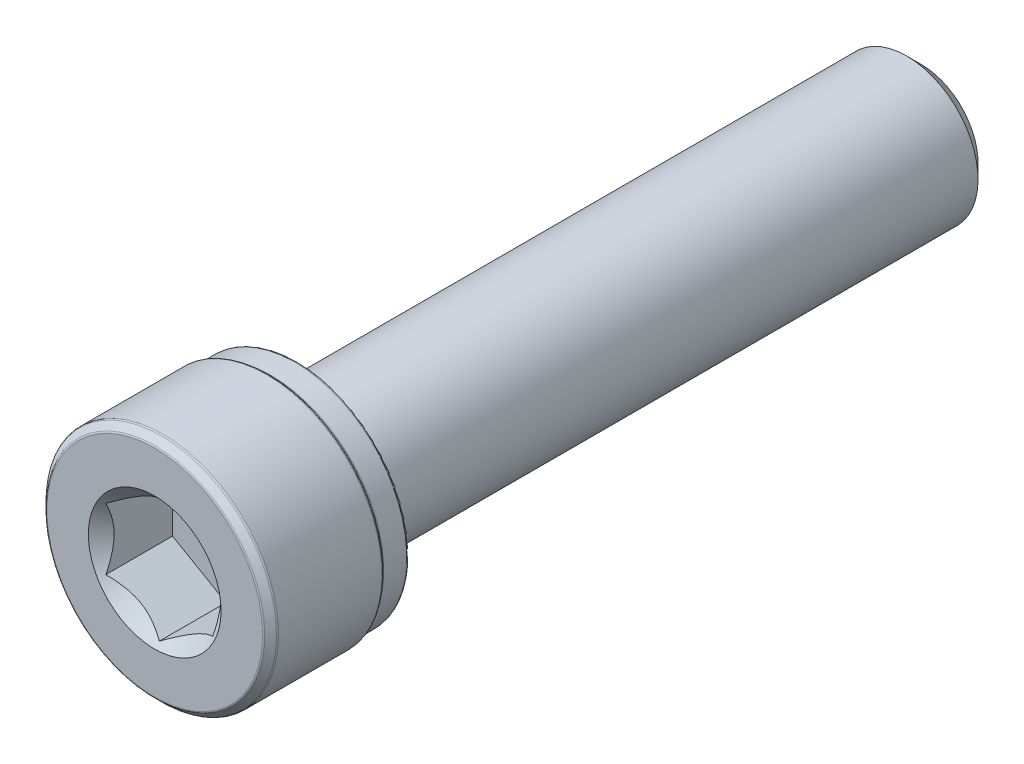
SolidWorks part; units mm, degrees
ref_plane "Front Plane" through (0, 0, 0) normal (0, 0, 1) x (1, 0, 0)
ref_plane "Top Plane" through (0, 0, 0) normal (0, 1, 0) x (1, 0, 0)
ref_plane "Right Plane" through (0, 0, 0) normal (1, 0, 0) x (0, 0, -1)
sketch "Sketch1" plane through (0, 0, 0) normal (1, 0, 0) x (0, 0, -1)
  line L0 (-21.5, 0) -> (21.5, 0) construction
  line L1 (21.5, 0) -> (21.5, 3.1881) construction
  line L2 (21.5, 3.1881) -> (20.6881, 4) construction
  line L3 (20.6881, 4) -> (20.5625, 4) construction
  line L4 (20.5625, 4) -> (-13.5, 4) construction
  line L5 (-13.5, 4) -> (-13.5, 6.5) construction
  line L6 (-13.5, 6.5) -> (-21.5, 6.5) construction
  line L7 (-21.5, 6.5) -> (-21.5, 0) construction
  line L8 (21.5, 3.1881) -> (21.5, 4) construction
  line L9 (21.4219, 4.1353) -> (22.0469, 3.0528) construction
  line L10 (22.0469, 3.0528) -> (22.6719, 4.1353) construction
  line L11 (22.6719, 4.1353) -> (21.4219, 4.1353) construction
  line L12 (22.0469, 4.1353) -> (22.0469, 4) construction
  line L13 (22.0469, 3.0528) -> (22.0469, 3.1881) construction
  line L14 (21.9688, 3.1881) -> (22.125, 3.1881) construction
  line L15 (21.5, 4) -> (22.5938, 4) construction
  line L16 (21.4609, 4.0677) -> (22.6328, 4.0677) construction
  line L17 (21.5, 0) -> (21.5, -4) construction
  line L18 (-13.9, 6.5) -> (-13.5, 6.1) construction
  line L19 (-21.1, 6.5) -> (-21.5, 6.1) construction
  line L20 (-13.5, 4) -> (-13.5, 0) construction
  line L21 (-13.5, 2) -> (-1.8333, 2) construction
  line L22 (-1.8333, 2) -> (9.8333, 2) construction
  line L23 (9.8333, 2) -> (21.5, 2) construction
  line L24 (-1.8333, 2) -> (-1.8333, 4) construction
  line L25 (-1.8333, 4) -> (-1.8333, 6.5) construction
  line L26 (9.8333, 2) -> (9.8333, 6.5) construction
  point P0 (-21.5, 3)
  point P3 (18.375, 4)
  point P4 (0, 0)
  point P18 (9.8333, 4)
  point P22 (22.0469, 3.1881)
  point P24 (20.5625, 4)
  point P25 (22.0469, 4)
  point P28 (22.0469, 4.0677)
  point P29 (18.375, -4)
  point P30 (-1.8333, 4)
  point P31 (-17.5, 6.5)
  point P37 (-14.9, 6.5)
  point P38 (-20.9, 6.5)
  point P45 (-1.8333, 2)
  point P46 (9.8333, 2)
  dimension "D1" = 45
  dimension "D2" = 0.1562
  dimension "D7" = 0.4
  dimension "D8" = 0.4
  dimension "D9" = 0.4
  dimension "D10" = 0.2
  dimension "D11" = 1
  dimension "Drive Size" = 6
  dimension "Head Diameter" = 13
  dimension "Head Height" = 8
  dimension "Thread Pitch" = 1.25
  dimension "Thread Dia" = 8
  dimension "Length" = 35
  dimension "D12" = 0.9375
  dimension "D4" = 3.125
  dimension "Key Engagement" = 4
sketch "Sketch2" plane through (0, 0, 0) normal (1, 0, 0) x (0, 0, -1)
  line L0 (-21.5, 0) -> (-21.5, 6.0482)
  line L1 (-21.0482, 6.5) -> (-15.2518, 6.5)
  line L2 (-13.5, 6.1375) -> (-13.5, 4.4)
  line L4 (20.6881, 4) -> (21.5, 3.1881)
  line L5 (21.5, 3.1881) -> (21.5, 0)
  line L6 (-13.5, 6.5) -> (-21.5, 6.5) construction
  line L7 (21.5, 0) -> (-21.5, 0)
  line L8 (-21.1, 6.5) -> (-21.5, 6.1) construction
  line L10 (-21.1366, 6.4634) -> (-21.4634, 6.1366)
  line L12 (-14.9482, 6.3) -> (-13.6625, 6.3)
  line L14 (-13.9, 6.5) -> (-13.5, 6.1) construction
  line L15 (-15.1634, 6.4634) -> (-15.0366, 6.3366)
  line L17 (-13.5, 4) -> (-13.5, 6.5) construction
  line L19 (-13.1, 4) -> (20.6881, 4)
  line L20 (20.5625, 4) -> (-13.5, 4) construction
  arc A0 (-13.6625, 6.3) -> (-13.5, 6.1375) centre (-13.6625, 6.1375) cw
  arc A1 (-13.5, 4.4) -> (-13.1, 4) centre (-13.1, 4.4) ccw
  arc A2 (-21.1366, 6.4634) -> (-21.0482, 6.5) centre (-21.0482, 6.375) cw
  arc A3 (-21.4634, 6.1366) -> (-21.5, 6.0482) centre (-21.375, 6.0482) ccw
  arc A4 (-15.1634, 6.4634) -> (-15.2518, 6.5) centre (-15.2518, 6.375) ccw
  arc A5 (-15.0366, 6.3366) -> (-14.9482, 6.3) centre (-14.9482, 6.425) ccw
  point P22 (-13.7, 6.3)
  point P37 (-15, 6.3)
  dimension "D2" = 0.1625
  dimension "D3" = 0.4
  dimension "D4" = 0.125
  dimension "D1" = 1.5
revolve "Revolve1" add sketch "Sketch2" angle 360 about L7
sketch "Sketch3" plane through (0, 0, 21.5) normal (0, 0, 1) x (1, 0, 0)
  line L1 (3, -1.7321) -> (3, 1.7321)
  line L2 (3, 1.7321) -> (0, 3.4641)
  line L3 (0, 3.4641) -> (-3, 1.7321)
  line L4 (-3, 1.7321) -> (-3, -1.7321)
  line L5 (-3, -1.7321) -> (0, -3.4641)
  line L6 (0, -3.4641) -> (3, -1.7321)
  circle A0 centre (0, 0) radius 3 construction
  circle A1 centre (0, 0) radius 6.5 construction
  circle A2 centre (0, 0) radius 6.5 construction
  circle A3 centre (0, 0) radius 3.4641 construction
  dimension "D1" = 6.9282
extrude "Cut-Extrude1" cut sketch "Sketch3" against normal up to vertex (4 mm away) up to point (0, 6.5, 17.5)
sketch "Sketch4" plane through (0, 0, 21.5) normal (0, 0, 1) x (1, 0, 0)
  circle A0 centre (0, 0) radius 3.7239
  dimension "D1" = 7.4478
extrude "Cut-Extrude2" cut sketch "Sketch4" against normal up to vertex (4 mm away) draft 45 up to point (0, 6.5, 17.5)
sketch "Sketch6" [suppressed] plane through (0, 0, -21.5) normal (0, 0, -1) x (-1, 0, 0)
  circle A0 centre (0, 0) radius 4
curve "Helix/Spiral1" [suppressed] pitch 1.25 height 36.25 turns 29
sketch "Sketch7" [suppressed] plane through (0, 0, 0) normal (1, 0, 0) x (0, 0, -1)
  line L0 (21.4609, 4.0677) -> (22.6328, 4.0677)
  line L1 (22.6328, 4.0677) -> (22.125, 3.1881)
  line L2 (22.125, 3.1881) -> (21.9688, 3.1881)
  line L3 (21.9688, 3.1881) -> (21.4609, 4.0677)
sweep "Cut-Sweep1" [suppressed] cut profiles "Sketch7" path "Helix/Spiral1"
sketch "Sketch8" [suppressed] plane through (0, 0, 0) normal (1, 0, 0) x (0, 0, -1)
  line L0 (-17.5, 0) -> (-17.5, 4.4)
  line L1 (-17.5, 1.7321) -> (-17.5, 3.4641) construction
  line L2 (-13.1, 4) -> (-12.875, 4)
  line L3 (-13.5, 4.4) -> (-17.5, 4.4)
  line L4 (-12.875, 4) -> (-10.5656, 0)
  line L5 (-10.5656, 0) -> (-17.5, 0)
  line L7 (-21.5, 0) -> (21.5, 0) construction
  line L8 (-13.5, 4) -> (-13.5, 6.5) construction
  arc A0 (-13.5, 4.4) -> (-13.1, 4) centre (-13.1, 4.4) ccw construction
  arc A1 (-13.5, 4.4) -> (-13.1, 4) centre (-13.1, 4.4) ccw
  dimension "D1" = 60
  dimension "D2" = 0.625
revolve "Revolve2" [suppressed] add sketch "Sketch8" angle 360 about L5
sketch "Sketch9" [suppressed] plane through (0, 0, 21.5) normal (0, 0, 1) x (1, 0, 0)
  line L0 (-0.0297, 6.3662) -> (-0.1625, 6.6628)
  line L1 (-0.1625, 6.6628) -> (0.1625, 6.6628)
  line L2 (0.1625, 6.6628) -> (0.0297, 6.3662)
  line L3 (0, 6.5) -> (0, 6.1) construction
  line L4 (0, 0) -> (-0.1625, 6.6628) construction
  line L5 (0.1625, 6.6628) -> (0, 0) construction
  circle A0 centre (0, 0) radius 6.3 construction
  arc A4 (-0.0297, 6.3662) -> (0.0297, 6.3662) centre (0, 6.3795) ccw
  point P10 (0, 6.3)
  point P19 (0, 6.3)
  dimension "D2" = 0.0325
  dimension "D1" = 0.325
  dimension "D3" = 2.794
extrude "Cut-Extrude3" [suppressed] cut sketch "Sketch9" against normal through all
pattern_circular "CirPattern1" [suppressed] count 80 over 360 of bodies 112
equation "\"D2@Sketch1\" = \"Thread Pitch@Sketch1\" / 8"
equation "\"D4@Helix/Spiral1\" = \"Thread Pitch@Sketch1\""
equation "\"D7@Sketch1\" = \"Head Height@Sketch1\" * .05"
equation "\"D8@Sketch1\"=\"D7@Sketch1\""
equation "\"D9@Sketch1\"=\"D7@Sketch1\""
equation "\"D10@Sketch1\"=\"D7@Sketch1\"/2"
equation "\"D11@Sketch1\"=\"D10@Sketch1\"*5"
equation "\"D4@Sketch1\"=\"Thread Pitch@Sketch1\"*2.5"
equation "\"D12@Sketch1\"=\"Thread Pitch@Sketch1\"*.75"
equation "\"D3@Helix/Spiral1\"=\"Length@Sketch1\"+\"Thread Pitch@Sketch1\""
equation "\"D1@Sketch2\"=\"Head Height@Sketch1\"*0.1875"
equation "\"D2@Sketch2\"=\"Head Diameter@Sketch1\"*0.0125"
equation "\"D3@Sketch2\"=\"Thread Dia@Sketch1\"*0.05"
equation "\"D1@Sketch9\"=\"Head Diameter@Sketch1\"*0.025"
equation "\"D2@Sketch9\"=\"D1@Sketch9\"*0.1"
equation "\"D2@Sketch8\"=\"Thread Pitch@Sketch1\"*00.5"
equation "\"D4@Sketch2\"=\"D8@Sketch1\"*0.3125"
equation "\"D1@CirPattern1\"=int ((360/\"D3@Sketch9\")*0.625)"
equation "\"D1@Sketch4\"=\"D1@Sketch3\" * 01.075"
